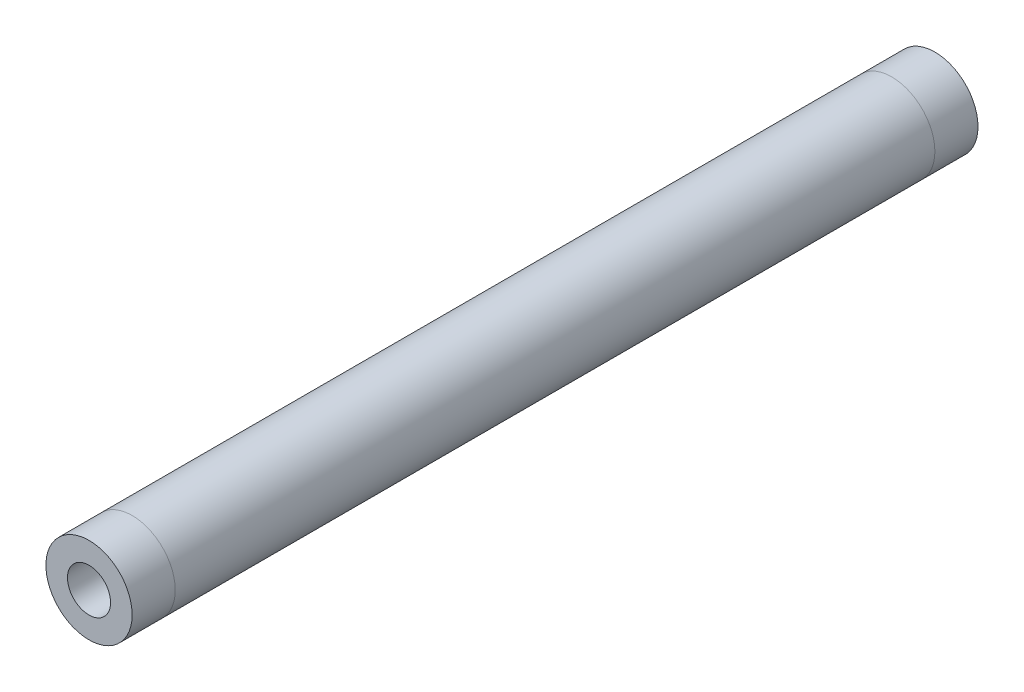
SolidWorks part; units mm, degrees
material "AISI 4130 Steel, normalized at 870C"
ref_plane "Front Plane" through (0, 0, 0) normal (0, 0, 1) x (1, 0, 0)
ref_plane "Top Plane" through (0, 0, 0) normal (0, 1, 0) x (1, 0, 0)
ref_plane "Right Plane" through (0, 0, 0) normal (1, 0, 0) x (0, 0, -1)
sketch "Axis" plane through (0, 0, 0) normal (0, 1, 0) x (1, 0, 0)
  line L0 (0, 0) -> (0, 21.9075) construction
  line L1 (0, 21.9075) -> (0, 146.5011) construction
  line L2 (0, 146.5011) -> (0, 168.4086) construction
  dimension "D1" = 21.9075
  dimension "D2" = 168.4086
sketch "Sketch2" plane through (0, 0, 0) normal (0, 0, 1) x (1, 0, 0)
  circle A0 centre (0, 0) radius 6.35
  circle A1 centre (0, 0) radius 3.175
  circle A2 centre (0, 0) radius 4.7625
  dimension "D1" = 12.7
  dimension "D2" = 6.35
  dimension "D3" = 9.525
extrude "Threaded Insert 1-1" add sketch "Sketch2" against normal blind 6.35 from vertex contours A0 A2 | A2 A1 region at (-6.1704, 0, 0) region at (-4.6278, 0, 0) starting at point (0, 0, -21.9075)
extrude "Threaded Insert 1-2" add sketch "Sketch2<5>" against normal blind 6.35 from surface contours A2 A1 region at (-4.6278, 0, 0) starting at face at (6.35, 0, -28.2575)
sketch "Sketch2<5>" plane through (0, 0, 0) normal (0, 0, 1) x (1, 0, 0) same geometry as "Sketch2"
extrude "Boss-Extrude4" add sketch "Sketch2<7>" along normal blind 6.35 from vertex separate body contours A0 A2 | A2 A1 region at (-6.1704, 0, 0) region at (-4.6278, 0, 0) starting at point (0, 0, -146.5011)
sketch "Sketch2<7>" plane through (0, 0, 0) normal (0, 0, 1) x (1, 0, 0) same geometry as "Sketch2"
extrude "Boss-Extrude5" add sketch "Sketch2<8>" along normal blind 6.35 from surface contours A2 A1 region at (-4.6278, 0, 0) starting at face at (6.35, 0, -140.1511)
sketch "Sketch2<8>" plane through (0, 0, 0) normal (0, 0, 1) x (1, 0, 0) same geometry as "Sketch2"
extrude "Boss-Extrude6" add sketch "Sketch2<9>" against normal up to surface (140.1511 mm away) from surface separate body contours A0 A2 region at (-6.1704, 0, 0) up to face at (6.35, 0, -140.1511) starting at face at (4.7625, 0, -28.2575)
sketch "Sketch2<9>" plane through (0, 0, 0) normal (0, 0, 1) x (1, 0, 0) same geometry as "Sketch2"
equation "\"Tube Outer Diameter\"= .5"
equation "\"Tube Inner Diameter\"= .375"
equation "\"Rod end Diameter\"= .25"
equation "\"Threaded Insert Out\"= .25"
equation "\"Threaded Insert In\"= .25'`"
equation "\"D1@Sketch2\"=\"Tube Outer Diameter\""
equation "\"D2@Sketch2\"=\"Rod end Diameter\""
equation "\"D1@Threaded Insert 1-1\" = \"Threaded Insert Out\""
equation "\"D3@Sketch2\"=\"Tube Inner Diameter\""
equation "\"D1@Threaded Insert 1-2\" = \"Threaded Insert In\""
equation "\"D1@Boss-Extrude4\"=\"Threaded Insert Out\""
equation "\"D1@Boss-Extrude5\"=\"Threaded Insert In\""
